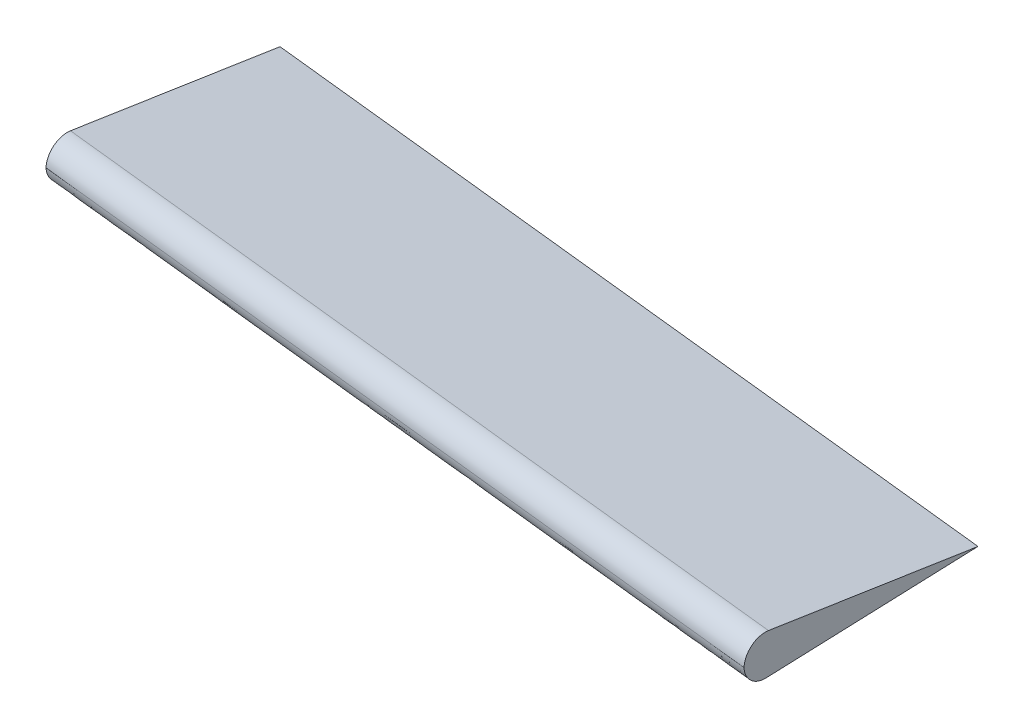
SolidWorks part; units mm, degrees
material "PET"
ref_plane "Alzado" through (0, 0, 0) normal (0, 0, 1) x (1, 0, 0)
ref_plane "Planta" through (0, 0, 0) normal (0, 1, 0) x (1, 0, 0)
ref_plane "Vista lateral" through (0, 0, 0) normal (1, 0, 0) x (0, 0, -1)
ref_plane "Plano2" through (184.57, 0, 0) normal (1, 0, 0) x (0, 0, -1)
sketch "Croquis11" plane through (0, 0, 0) normal (1, 0, 0) x (0, 0, -1)
  line L0 (-27.625, 5.2383) -> (27.625, -3.1759)
  line L1 (27.625, -3.1759) -> (-27.625, -5.2383)
  line L2 (-27.625, -5.2383) -> (-27.625, 5.2383)
  dimension "D1" = 10.4766
  dimension "D2" = 55.887
  dimension "D3" = 55.2885
sketch "Croquis12" plane through (184.57, 0, 0) normal (1, 0, 0) x (0, 0, -1)
  line L0 (-47.415, 5.2383) -> (7.835, -3.1759)
  line L1 (7.835, -3.1759) -> (-47.415, -5.2417)
  line L2 (-47.415, -5.2417) -> (-47.415, 5.2383)
  line L3 (-27.625, 5.2383) -> (-48.4234, 5.2383) construction
  dimension "D1" = 19.79
  dimension "D2" = 10.48
  dimension "D3" = 55.887
loft "Recubrir2" add profiles "Croquis12", "Croquis11" connector at (184.57, 5.2383, 47.415) connector at (0, 5.2383, 27.625)
fillet "Redondeo2" radius 5 2 edges
